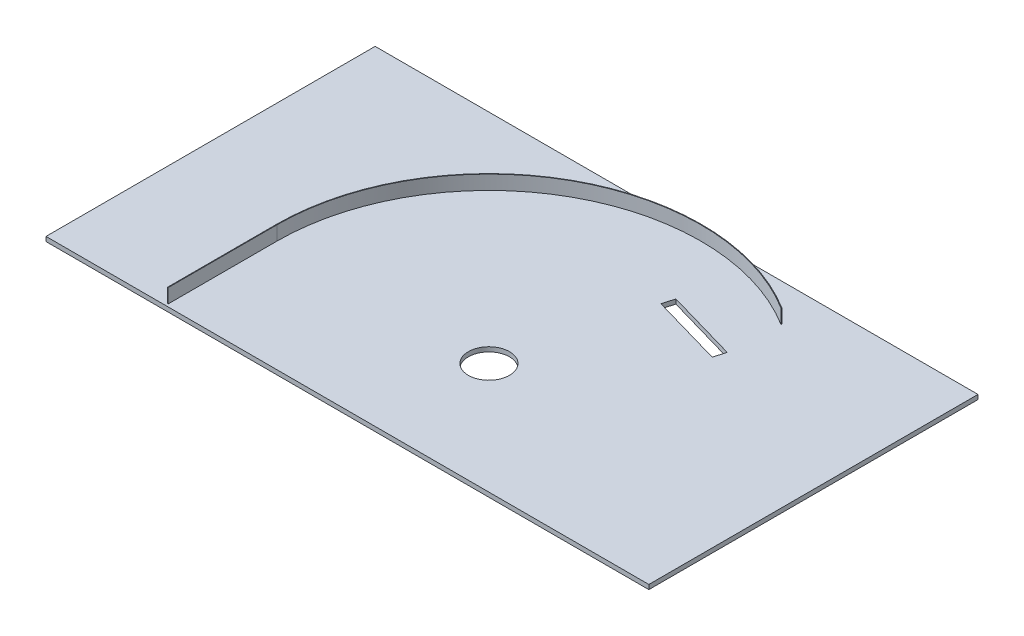
SolidWorks part; units mm, degrees
material "Particle Board"
ref_plane "Front Plane" through (0, 0, 0) normal (0, 0, 1) x (1, 0, 0)
ref_plane "Top Plane" through (0, 0, 0) normal (0, 1, 0) x (1, 0, 0)
ref_plane "Right Plane" through (0, 0, 0) normal (1, 0, 0) x (0, 0, -1)
sketch "Sketch3" plane through (0, 0, 0) normal (0, 1, 0) x (1, 0, 0)
  line L1 (0, 0) -> (-839.8654, 0) construction
  line L2 (0, 0) -> (-451.1992, 260.5) construction
  line L5 (-524, 0) -> (-525.5875, 0)
  line L6 (277.6777, 444.3772) -> (277.6777, 446.248)
  circle A0 centre (0, 0) radius 254 construction
  arc A3 (277.6777, 444.3772) -> (-524, 0) centre (0, 0) ccw
  arc A4 (277.6777, 446.248) -> (-525.5875, 0) centre (0, 0) ccw
  arc A5 (278.5189, 445.7235) -> (-525.5875, 0) centre (0, 0) ccw construction
  dimension "D1" = 524
  dimension "D2" = 1.5875
  dimension "D4" = 122
  dimension "D5" = 508
  dimension "D3" = 30
extrude "Boss-Extrude1" add sketch "Sketch3" along normal blind 35
sketch "Sketch4" plane through (0, 0, 0) normal (0, 1, 0) x (1, 0, 0)
  line L0 (-538.2597, 525.5875) -> (609.3192, 525.5875) construction
  line L5 (-819.5875, 538.2875) -> (670.6777, 538.2875)
  line L6 (-819.5875, 538.2875) -> (-819.5875, -275.4)
  line L7 (-819.5875, -275.4) -> (670.6777, -275.4)
  line L8 (670.6777, 538.2875) -> (670.6777, -275.4)
  arc A0 (277.6777, 446.248) -> (-525.5875, 0) centre (0, 0) ccw construction
  dimension "D1" = 275.4
  dimension "D2" = 294
  dimension "D3" = 12.7
  dimension "D4" = 393
extrude "Boss-Extrude2" add sketch "Sketch4" against normal blind 11.1125
hole_wizard "Ø20.0mm Dowel Hole1" positions "Sketch6" profile "Sketch7" hole size "Ø20.0" standard "ANSI Metric" end condition through all
sketch "Sketch6" plane through (0, 0, 0) normal (0, 1, 0) x (1, 0, 0)
  point P0 (0, 0)
sketch "Sketch7" plane through (0, 0, 0) normal (1, 0, 0) x (0, 0, 1)
  line L0 (0, 0) -> (0, 11.1125)
  line L1 (0, 11.1125) -> (50.8, 11.1125)
  line L2 (50.8, 11.1125) -> (50.8, 0)
  line L5 (50.8, 0) -> (0, 0)
  line L11 (0, -6.35) -> (0, 107.95) construction
  dimension "Thru Hole Dia." = 101.6
  dimension "Thru Hole Depth" = 11.1125
ref_plane "Plane1" through (0, 0, 269.05) normal (0, 0, 1) x (1, 0, 0)
sketch "Sketch8" plane through (0, 0, 0) normal (0, 0, 1) x (1, 0, 0)
  line L1 (-525.5875, 35) -> (-524, 35)
  line L2 (-525.5875, 35) -> (-525.5875, 0)
  line L3 (-525.5875, 0) -> (-524, 0)
  line L4 (-524, 35) -> (-524, 0)
extrude "Boss-Extrude3" add sketch "Sketch8" along normal up to surface (269.05 mm away) up to plane "Plane1"
sketch "Sketch9" plane through (0, 0, 0) normal (0, 1, 0) x (1, 0, 0)
  line L0 (270.6777, 318.2875) -> (92.8443, 369.2804)
  line L1 (92.8443, 369.2804) -> (84.5752, 340.4426)
  line L2 (84.5752, 340.4426) -> (262.4086, 289.4496)
  line L3 (262.4086, 289.4496) -> (270.6777, 318.2875)
  line L4 (670.6777, 538.2875) -> (-819.5875, 538.2875) construction
  line L5 (670.6777, -275.4) -> (670.6777, 538.2875) construction
  dimension "D1" = 185
  dimension "D2" = 30
  dimension "D3" = 16
  dimension "D4" = 400
  dimension "D5" = 220
extrude "Cut-Extrude1" cut sketch "Sketch9" against normal through all
